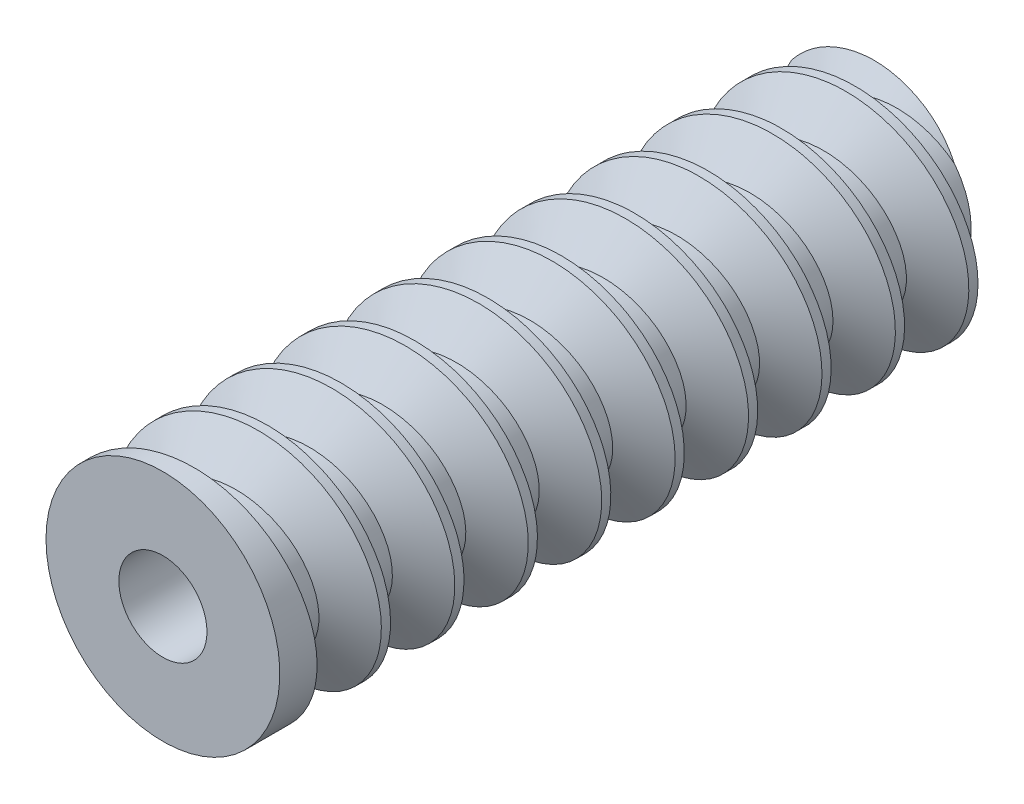
SolidWorks part; units mm, degrees
material "PET"
ref_plane "Front Plane" through (0, 0, 0) normal (0, 0, 1) x (1, 0, 0)
ref_plane "Top Plane" through (0, 0, 0) normal (0, 1, 0) x (1, 0, 0)
ref_plane "Right Plane" through (0, 0, 0) normal (1, 0, 0) x (0, 0, -1)
sketch "Sketch1" plane through (0, 0, 0) normal (0, 0, 1) x (1, 0, 0)
  circle A0 centre (0, 0) radius 3.98
  dimension "D1" = 7.96
extrude "Boss-Extrude1" add sketch "Sketch1" along normal blind 24.89
thread "Thread1" pitch 2.5 method cut profile "Thread Profile1" start angle 0, offset 0, length 30, pitch 2.5, diameter 7.96
ref_plane "Plane1" through (-3.98, 0, 24.89) normal (0, -1, 0) x (-1, 0, 0)
sketch "Thread Profile1" plane through (-3.98, 0, 24.89) normal (0, -1, 0) x (-1, 0, 0)
  line L0 (0, 0) -> (0, 2.5) construction
  line L11 (0, 0) -> (0, 2.1875)
  line L12 (0, 2.1875) -> (-1.3532, 1.4062)
  line L13 (-1.3532, 1.4062) -> (-1.3532, 0.7812)
  line L15 (-1.3532, 0.7812) -> (0, 0)
  line L17 (-1.3532, 1.0937) -> (0, 1.0937) construction
  point P2 (0, 0)
  dimension "Pitch" = 2.5
  dimension "Profile_Angle" = 60
  dimension "Profile_Land" = 0.625
  dimension "Profile_Height" = 1.3532
sketch "Sketch7" plane through (0, 0, 24.89) normal (0, 0, 1) x (1, 0, 0)
  circle A0 centre (0, 0) radius 1.5
  dimension "D1" = 3
extrude "Cut-Extrude1" cut sketch "Sketch7" against normal through all contours A0
